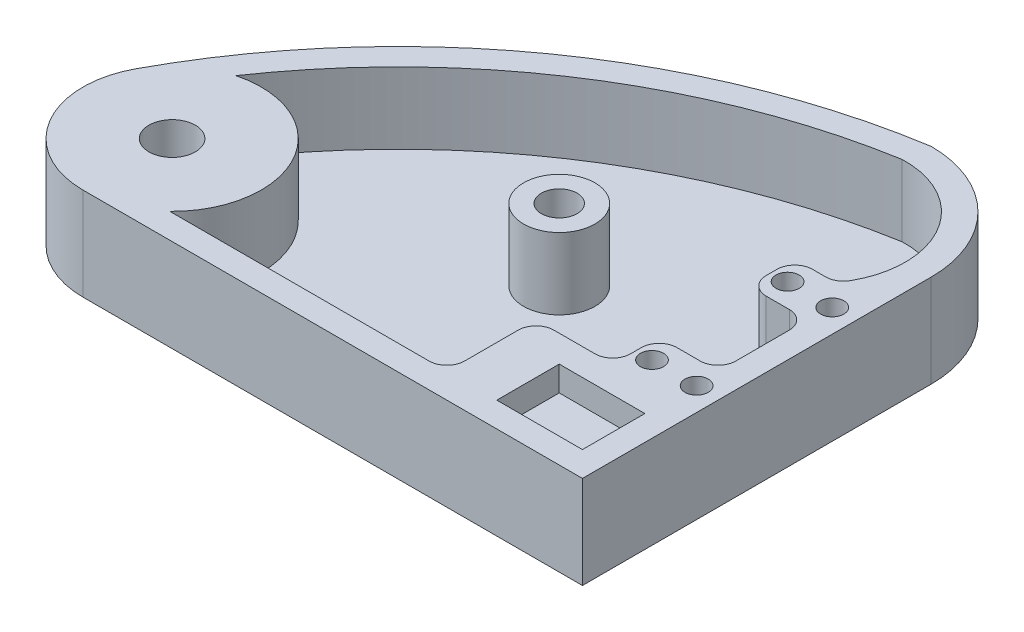
SolidWorks part; units mm, degrees
ref_plane "Front Plane" through (0, 0, 0) normal (0, 0, 1) x (1, 0, 0)
ref_plane "Top Plane" through (0, 0, 0) normal (0, 1, 0) x (1, 0, 0)
ref_plane "Right Plane" through (0, 0, 0) normal (1, 0, 0) x (0, 0, -1)
sketch "Sketch1" plane through (0, 0, 0) normal (0, 1, 0) x (1, 0, 0)
  line L0 (0, 0) -> (0, 32138.1491) construction
  line L1 (0, 0) -> (32138.1491, 0) construction
  line L2 (-70, -63.5) -> (70, -63.5)
  line L3 (70, -63.5) -> (70, 34.2173)
  line L4 (-52.6506, -56.5) -> (20, -56.5)
  line L5 (25, -51.5) -> (25, -36.5)
  line L6 (30, -31.5) -> (41.5, -31.5)
  line L7 (46.5, -26.5) -> (46.5, -23.5)
  line L8 (51.5, -18.5) -> (58, -18.5)
  line L9 (63, -13.5) -> (63, 1.5)
  line L10 (58, 6.5) -> (51.5, 6.5)
  line L11 (46.5, 11.5) -> (46.5, 14.5)
  line L12 (51.5, 19.5) -> (55.178, 19.5)
  line L14 (39, -56.5) -> (63, -56.5)
  line L15 (39, -56.5) -> (39, -39)
  line L16 (39, -39) -> (63, -39)
  line L17 (63, -56.5) -> (63, -39)
  line L18 (39, -56.5) -> (63, -39) construction
  line L19 (39, -39) -> (63, -56.5) construction
  circle A0 centre (0, 0) radius 5
  circle A1 centre (0, 0) radius 10
  circle A2 centre (-70, -38.5) radius 25
  arc A3 (70, 34.2173) -> (38.25, 65.9673) centre (38.25, 34.2173) ccw
  arc A5 (38.25, 65.9673) -> (-92.0288, -26.6791) centre (66.5783, -111.7896) ccw
  arc A6 (37.3209, 58.7185) -> (-76.3507, -14.3201) centre (66.5783, -111.7896) ccw
  circle A7 centre (-70, -38.5) radius 6.5
  circle A8 centre (51, 13) radius 3.25
  circle A9 centre (63.5, 13) radius 3.25
  circle A10 centre (51, -25) radius 3.25
  circle A11 centre (63.5, -25) radius 3.25
  arc A12 (55.178, 19.5) -> (59.5144, 22.0108) centre (55.178, 24.5) ccw
  arc A13 (46.5, 14.5) -> (51.5, 19.5) centre (51.5, 14.5) cw
  arc A14 (59.5144, 22.0108) -> (37.3209, 58.7185) centre (38.25, 34.2173) ccw
  arc A15 (51.5, 6.5) -> (46.5, 11.5) centre (51.5, 11.5) cw
  arc A16 (63, 1.5) -> (58, 6.5) centre (58, 1.5) ccw
  arc A17 (58, -18.5) -> (63, -13.5) centre (58, -13.5) ccw
  arc A18 (46.5, -23.5) -> (51.5, -18.5) centre (51.5, -23.5) cw
  arc A19 (41.5, -31.5) -> (46.5, -26.5) centre (41.5, -26.5) ccw
  arc A20 (25, -36.5) -> (30, -31.5) centre (30, -36.5) cw
  arc A21 (20, -56.5) -> (25, -51.5) centre (20, -51.5) ccw
  point P16 (51, -47.75)
  point P46 (46.5, 19.5)
  point P50 (46.5, 6.5)
  point P53 (63, 6.5)
  point P56 (63, -18.5)
  point P59 (46.5, -18.5)
  point P62 (46.5, -31.5)
  point P65 (25, -31.5)
  point P68 (25, -56.5)
  point P69 (63.5, -26.1079)
  point P70 (63, -26.1079)
  dimension "D1" = 10
  dimension "D2" = 20
  dimension "D3" = 50
  dimension "D5" = 63.5
  dimension "D8" = 25
  dimension "D9" = 140
  dimension "D21" = 180
  dimension "D23" = 13
  dimension "D22" = 7
  dimension "D25" = 6.5
  dimension "D6" = 5
  dimension "D4" = 38.5
  dimension "D10" = 25
  dimension "D11" = 45
  dimension "D12" = 7
  dimension "D7" = 13
  dimension "D13" = 13
  dimension "D14" = 25
  dimension "D15" = 7
  dimension "D16" = 23.5
  dimension "D17" = 17.5
  dimension "D18" = 24
  dimension "D19" = 7
  dimension "D20" = 7
  dimension "D24" = 6.5
  dimension "D26" = 6.5
  dimension "D27" = 12.5
  dimension "D28" = 12.5
  dimension "D29" = 38
  dimension "D30" = 38
  dimension "D31" = 14
  dimension "D32" = 14
extrude "Boss-Extrude1" add sketch "Sketch1" along normal blind 26 contours A2 A7 | A21 L4 A2 L2 L3 A3 A5 A6 A14 A12 L12 A13 L11 A15 L10 A16 L9 A17 L8 A18 L7 A19 L6 A20 L5 A11 A10 A9 A8 L17 L14 L15 L16 region at (-60.5683, 0, 61.8764) region at (-90.8469, 0, 50.972)
extrude "Boss-Extrude2" add sketch "Sketch1<3>" along normal blind 6 contours L4 A21 L5 A20 L6 A19 L7 A18 L8 A17 L9 A16 L10 A15 L11 A13 L12 A12 A14 A6 A2 A1 region at (-45.3279, 0, 48.9866)
sketch "Sketch1<3>" plane through (0, 0, 0) normal (0, 1, 0) x (1, 0, 0) same geometry as "Sketch1"
extrude "Boss-Extrude3" add sketch "Sketch1<4>" along normal blind 19 contours L16 L17 L14 L15
sketch "Sketch1<4>" plane through (0, 0, 0) normal (0, 1, 0) x (1, 0, 0) same geometry as "Sketch1"
extrude "Boss-Extrude4" add sketch "Sketch1<5>" along normal blind 26 contours A1 A0 region at (-9.7172, 0, 0)
sketch "Sketch1<5>" plane through (0, 0, 0) normal (0, 1, 0) x (1, 0, 0) same geometry as "Sketch1"
